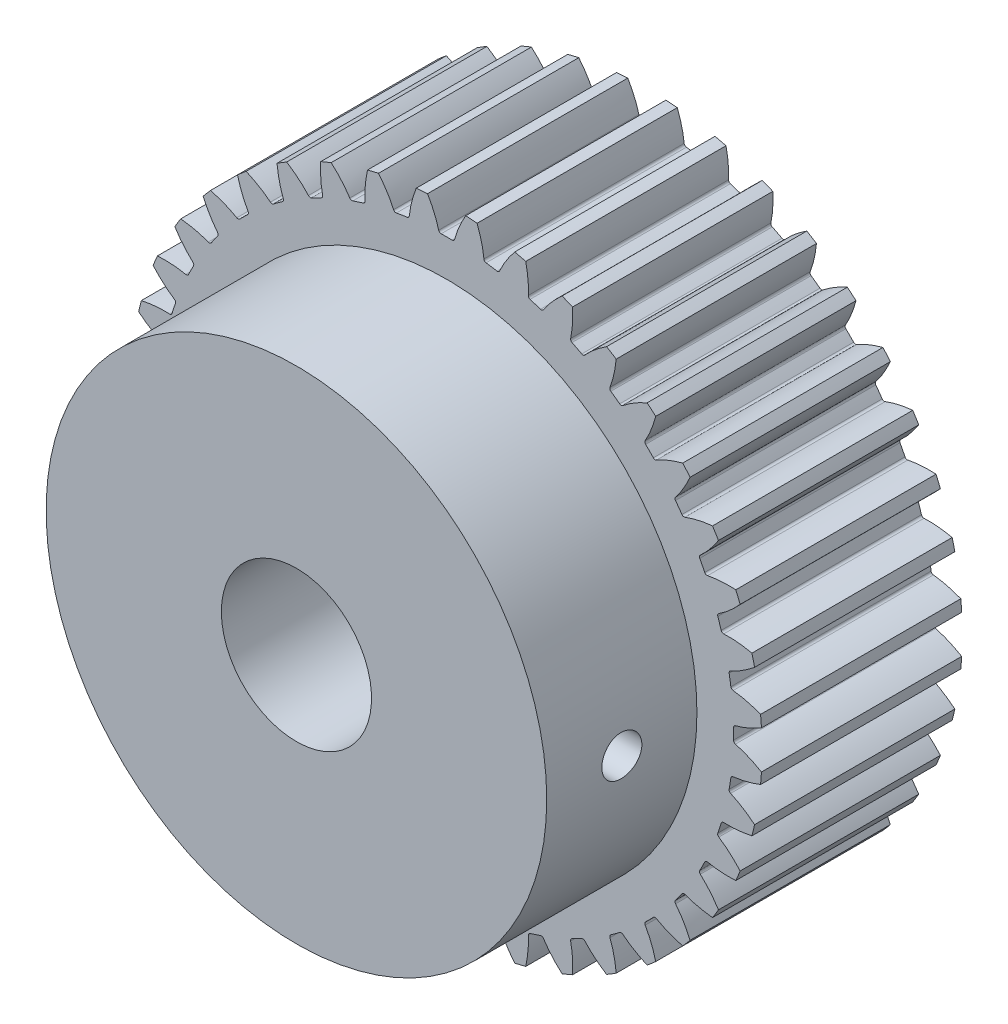
SolidWorks part; units mm, degrees
ref_plane "Front Plane" through (0, 0, 0) normal (0, 0, 1) x (1, 0, 0)
ref_plane "Top Plane" through (0, 0, 0) normal (0, 1, 0) x (1, 0, 0)
ref_plane "Right Plane" through (0, 0, 0) normal (1, 0, 0) x (0, 0, -1)
sketch "Sketch1" plane through (0, 0, 0) normal (0, 0, 1) x (1, 0, 0)
  line L0 (0, 30) -> (0, -30) construction
  line L1 (0, -30) -> (8.8305, -30) construction
  line L2 (0, -30) -> (9.6418, -26.4907) construction
  line L3 (0, 0) -> (9.6418, -26.4907)
  line L4 (0, 0) -> (-28.1284, 0) construction
  line L5 (-28.1284, 1.875) -> (-28.1284, -1.875) construction
  line L6 (-28.1284, 1.875) -> (0, 0) construction
  line L7 (0, 0) -> (-28.1284, -1.875) construction
  line L8 (0, 0) -> (-20.6686, 19.1711) construction
  line L9 (0, 0) -> (-17.9401, 21.7456) construction
  line L10 (0, 0) -> (-14.894, 23.9351) construction
  line L11 (0, 0) -> (-11.5842, 25.7007) construction
  line L12 (0, 0) -> (-8.0692, 27.0113) construction
  line L13 (0, 0) -> (-4.4113, 27.8435) construction
  line L14 (-4.4113, 27.8435) -> (-0.7075, 28.4303) construction
  line L15 (-8.0692, 27.0113) -> (-0.883, 29.158) construction
  line L16 (-11.5842, 25.7007) -> (-1.3279, 30.3236) construction
  line L17 (-14.894, 23.9351) -> (-2.1584, 31.86) construction
  line L18 (-17.9401, 21.7456) -> (-3.4769, 33.6778) construction
  line L19 (-20.6686, 19.1711) -> (-5.3675, 35.6673) construction
  circle A0 centre (0, 0) radius 28.1908 construction
  arc A1 (1.1779, 29.9769) -> (-1.1779, 29.9769) centre (0, 0) ccw construction
  circle A2 centre (0, 30) radius 1.1781 construction
  circle A3 centre (0, 0) radius 28.6595
  circle A4 centre (0, 0) radius 31.5
  circle A5 centre (0, 0) radius 7.5
  circle A6 centre (0, 0) radius 25
  spline S0 degree 3 poles (-5.3675, 35.6673) (-4.1503, 34.5369) (-2.6529, 32.8286) (-1.3674, 30.4884) (-0.9147, 29.3232) (-0.6834, 28.4341) (-0.6286, 27.5171) (-0.6989, 26.269) (-1.1981, 23.646) (-2.0942, 21.5586) (-2.9023, 20.1072) knots 0 0 0 0 0.285711 0.385711 0.45714 0.5 0.54286 0.614289 0.714289 1 1 1 1
  spline S1 degree 3 poles (5.3675, 35.6673) (4.1503, 34.5369) (2.6529, 32.8286) (1.3674, 30.4884) (0.9147, 29.3232) (0.6834, 28.4341) (0.6286, 27.5171) (0.6989, 26.269) (1.1981, 23.646) (2.0942, 21.5586) (2.9023, 20.1072) knots 0 0 0 0 0.285711 0.385711 0.45714 0.5 0.54286 0.614289 0.714289 1 1 1 1
  point P3 (-2.9023, 20.1072)
  point P4 (0, 0)
  point P16 (-28.1284, 0)
  point P27 (-1.7192, 22.5838)
  point P28 (-1.0272, 24.72)
  point P29 (-0.7123, 26.438)
  point P30 (-0.6494, 27.684)
  dimension "D4" = 2.3562
  dimension "D17" = 63
  dimension "D18" = 57.3191
  dimension "D19" = 15
  dimension "D20" = 50
  dimension "D1" = 20
  dimension "D2" = 60
  dimension "D3" = 90
  dimension "D5" = 3.75
  dimension "D6" = 7.63
  dimension "D7" = 7.63
  dimension "D8" = 7.63
  dimension "D9" = 7.63
  dimension "D10" = 7.63
  dimension "D11" = 3.75
  dimension "D12" = 7.5
  dimension "D13" = 11.25
  dimension "D14" = 15
  dimension "D15" = 18.75
  dimension "D16" = 22.5
extrude "Boss-Extrude1" add sketch "Sketch1" along normal blind 20 contours A4
extrude "Cut-Extrude2" cut sketch "Sketch1<5>" along normal through all contours S1 A4 S0 A3 region at (0, 30.2907, 0)
sketch "Sketch1<5>" plane through (0, 0, 0) normal (0, 0, 1) x (1, 0, 0) same geometry as "Sketch1"
fillet "Fillet1" radius 0.25 2 edges at (0.7485, 28.6498, 10) (-0.7485, 28.6498, 10)
pattern_circular "CirPattern1" count 40 over 360 about axis through (0, 0, 20) along (0, 0, -1) of "Cut-Extrude2", "Fillet1" reverse direction yes
extrude "Boss-Extrude2" add sketch "Sketch1<8>" along normal blind 35 contours A6
sketch "Sketch1<8>" plane through (0, 0, 0) normal (0, 0, 1) x (1, 0, 0) same geometry as "Sketch1"
sketch "Sketch2" plane through (0, 0, 0) normal (0, 0, -1) x (-1, 0, 0)
  circle A0 centre (0, 0) radius 7.5
  dimension "D1" = 15
extrude "Cut-Extrude4" cut sketch "Sketch2" against normal through all
ref_plane "Plane1" through (25, 0, 0) normal (1, 0, 0) x (0, 0, -1)
sketch "Sketch3" plane through (25, 0, 0) normal (1, 0, 0) x (0, 0, -1)
  line L0 (-35, 0) -> (0, 0) construction
  line L1 (-35, 25) -> (-35, -25) construction
  line L2 (-35, 0) -> (-27.5, 0) construction
  circle A0 centre (-27.5, 0) radius 2
  dimension "D1" = 7.5
extrude "Cut-Extrude5" cut sketch "Sketch3" against normal up to next
equation "\"boss\"= 50mm"
equation "\"bore\"= 15mm"
equation "\"pcd\"= 60mm"
equation "\"d\"= 63mm"
equation "\"e\"= 7.63"
equation "\"x\"= 3.75"
equation "\"y\"= 1"
equation "\"z\"= 1"
equation "\"D2@Sketch1\"=\"pcd\""
equation "\"D4@Sketch1\"=3/4*pi"
equation "\"D6@Sketch1\"=\"e\""
equation "\"D7@Sketch1\"=\"e\""
equation "\"D8@Sketch1\"=\"e\""
equation "\"D9@Sketch1\"=\"e\""
equation "\"D10@Sketch1\"=\"e\""
equation "\"D12@Sketch1\"=\"x\"*2"
equation "\"D13@Sketch1\"=\"x\"*3"
equation "\"D14@Sketch1\"=\"x\"*4"
equation "\"D15@Sketch1\"=\"x\"*5"
equation "\"D16@Sketch1\"=\"x\"*6"
equation "\"D17@Sketch1\"=\"d\""
equation "\"D19@Sketch1\"=\"bore\""
equation "\"D20@Sketch1\"=\"boss\""
equation "\"D1@Sketch2\"=\"bore\""
